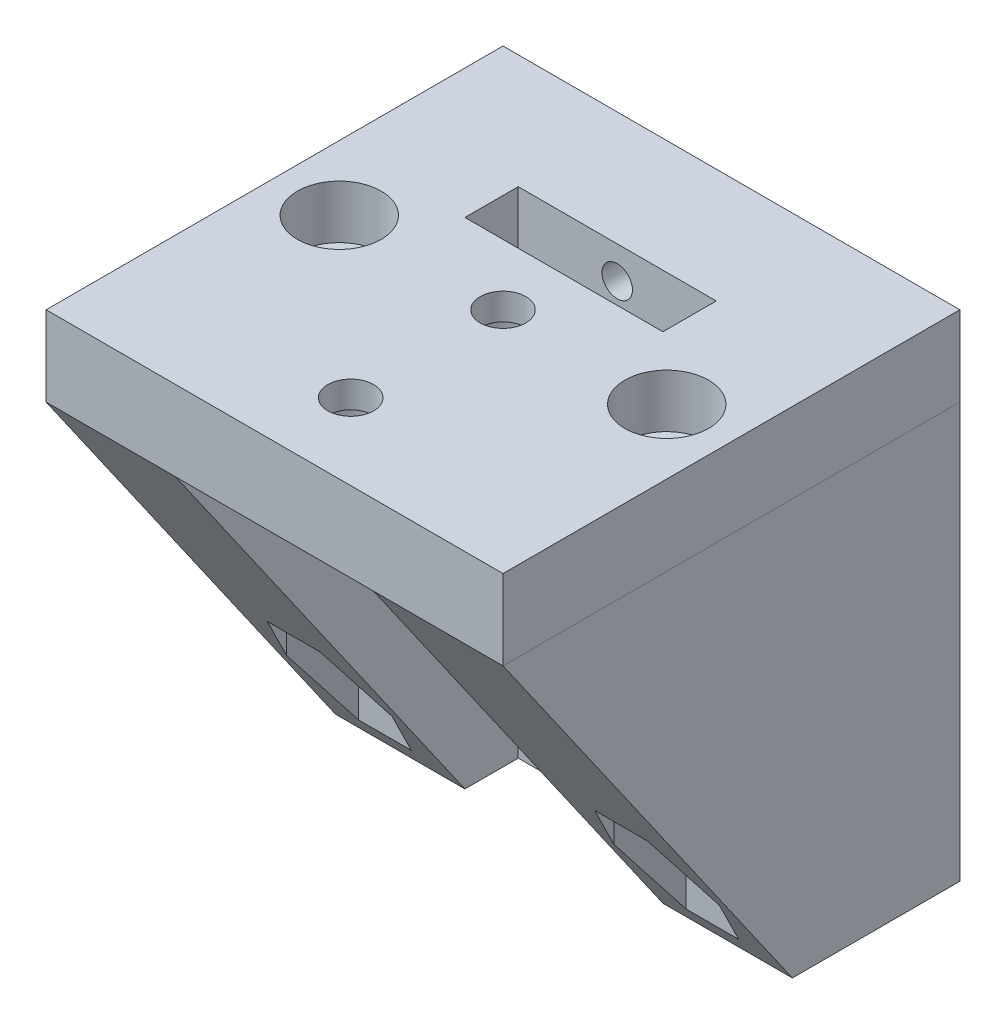
SolidWorks part; units mm, degrees
ref_plane "Front Plane" through (0, 0, 0) normal (0, 0, 1) x (1, 0, 0)
ref_plane "Top Plane" through (0, 0, 0) normal (0, 1, 0) x (1, 0, 0)
ref_plane "Right Plane" through (0, 0, 0) normal (1, 0, 0) x (0, 0, -1)
sketch "Sketch1" plane through (0, 0, 0) normal (0, 0, 1) x (1, 0, 0)
  line L0 (0, 0) -> (0, 50000) construction
  line L1 (0, 0) -> (50000, 0) construction
  line L2 (3.5, 6.35) -> (3.5, 5.2983)
  line L3 (-3.5, 6.35) -> (-3.5, 5.2983)
  line L4 (-15, 5.65) -> (49985, 5.65) construction
  line L5 (-15, -10.6) -> (15, -10.6)
  line L6 (-15, -10.6) -> (-15, 21.9)
  line L7 (-15, 21.9) -> (15, 21.9)
  line L8 (15, -10.6) -> (15, 21.9)
  line L9 (-6.5, -6.35) -> (6.5, -6.35)
  line L10 (-6.5, -6.35) -> (-6.5, 16.65)
  line L11 (-6.5, 16.65) -> (6.5, 16.65)
  line L12 (6.5, -6.35) -> (6.5, 16.65)
  arc A0 (-3.5, 5.2983) -> (3.5, 5.2983) centre (0, 0) ccw
  arc A1 (3.5, 6.35) -> (-3.5, 6.35) centre (0, 6.35) ccw
  arc A2 (-3.5, 5.2983) -> (3.5, 5.2983) centre (0, 0) ccw construction
  circle A3 centre (0, 0) radius 6.35 construction
  circle A4 centre (0, -8.475) radius 1
  circle A5 centre (0, 19.775) radius 1
  point P8 (0, -10.6)
  point P17 (0, -10.6)
  point P22 (0, 16.65)
  point P23 (0, -8.475)
  point P26 (-15, 5.65)
  dimension "D1" = 12.7
  dimension "D2" = 7
  dimension "D6" = 13
  dimension "D9" = 2
  dimension "D3" = 10.6
  dimension "D4" = 30
  dimension "D5" = 32.5
  dimension "D7" = 23
  dimension "D8" = 2.125
  dimension "D10" = 21.9
extrude "Boss-Extrude3" add sketch "Sketch1" along normal blind 1.5 contours L5 L8 L7 L6 L12 L9 L10 L11 A4 A5 region at (-14.5577, 5.65, 0)
sketch "Sketch6" plane through (0, 0, 0) normal (0, 0, -1) x (-1, 0, 0)
  line L1 (-15, -10.6) -> (15, -10.6)
  line L2 (-15, -10.6) -> (-15, 21.9)
  line L3 (-15, 21.9) -> (15, 21.9)
  line L4 (15, -10.6) -> (15, 21.9)
extrude "Boss-Extrude4" add sketch "Sketch6" along normal blind 6
extrude "Cut-Extrude1" cut sketch "Sketch1<3>" against normal up to surface (6 mm away) contours L2 A1 L3 A0 region at (0, 1.1131, 0) up to face at (0, 5.65, -6)
sketch "Sketch1<3>" plane through (0, 0, 0) normal (0, 0, 1) x (1, 0, 0) same geometry as "Sketch1"
sketch "Sketch7" plane through (0, 0, 1.5) normal (0, 0, 1) x (1, 0, 0)
  line L0 (-15, -10.6) -> (15, -10.6) construction
  line L2 (-15, 21.9) -> (-6.5, 21.9)
  line L3 (-15, 21.9) -> (-15, -10.6)
  line L4 (-15, -10.6) -> (-6.5, -10.6)
  line L5 (-6.5, 21.9) -> (-6.5, -10.6)
  line L6 (-15, 21.9) -> (15, 21.9) construction
  line L7 (15, -10.6) -> (6.5, -10.6)
  line L8 (15, -10.6) -> (15, 21.9)
  line L9 (15, 21.9) -> (6.5, 21.9)
  line L10 (6.5, -10.6) -> (6.5, 21.9)
  line L11 (6.5, -6.35) -> (6.5, 16.65) construction
  line L12 (-6.5, -6.35) -> (-6.5, 16.65) construction
extrude "Boss-Extrude5" add sketch "Sketch7" along normal blind 3.5
sketch "Sketch8" plane through (0, 0, 5) normal (0, 0, 1) x (1, 0, 0)
  line L0 (15, -10.6) -> (15, 21.9) construction
  line L1 (-15, 21.9) -> (15, 21.9)
  line L2 (-15, 21.9) -> (-15, 16.65)
  line L3 (-15, 16.65) -> (15, 16.65)
  line L4 (15, 21.9) -> (15, 16.65)
  line L5 (-6.5, 16.65) -> (6.5, 16.65) construction
extrude "Boss-Extrude6" add sketch "Sketch8" along normal blind 19
ref_plane "Plane1" through (15, 0, 0) normal (1, 0, 0) x (0, 0, -1)
sketch "Sketch9" plane through (15, 0, 0) normal (1, 0, 0) x (0, 0, -1)
  line L0 (-24, 16.65) -> (-5, 16.65)
  line L1 (-24, 16.65) -> (-5, 16.65) construction
  line L2 (-5, 16.65) -> (-5, -10.6)
  line L3 (-5, -10.6) -> (-24, 16.65)
extrude "Boss-Extrude7" add sketch "Sketch9" against normal up to surface (8.5 mm away) up to face at (6.5, 6.65, 2.3333)
ref_plane "Plane2" through (-15, 0, 0) normal (-1, 0, 0) x (0, 0, 1)
sketch "Sketch10" plane through (-15, 0, 0) normal (-1, 0, 0) x (0, 0, 1)
  line L0 (24, 16.65) -> (5, -10.6)
  line L1 (5, -10.6) -> (5, 16.65)
  line L2 (5, 16.65) -> (24, 16.65)
extrude "Boss-Extrude8" add sketch "Sketch10" against normal up to surface (8.5 mm away) up to face at (-6.5, 6.65, 2.3333)
sketch "Sketch12" plane through (0, 0, -6) normal (0, 0, -1) x (-1, 0, 0)
  line L0 (0, 0) -> (0, 50000) construction
  line L2 (2.3094, -8.6) -> (1.1547, -6.6)
  line L3 (1.1547, -6.6) -> (-1.1547, -6.6)
  line L4 (-1.1547, -6.6) -> (-2.3094, -8.6)
  line L5 (-2.3094, -8.6) -> (-1.1547, -10.6)
  line L6 (-1.1547, -10.6) -> (1.1547, -10.6)
  line L7 (1.1547, -10.6) -> (2.3094, -8.6)
  line L16 (-15, -10.6) -> (15, -10.6) construction
  circle A0 centre (0, -8.6) radius 2 construction
  dimension "D2" = 4
extrude "Cut-Extrude2" cut sketch "Sketch12" against normal blind 1.5
sketch "Sketch14" plane through (0, 0, 0) normal (0, 0, 1) x (1, 0, 0)
  line L0 (-1, -8.475) -> (49999, -8.475) construction
  line L1 (0, -7.475) -> (0, -50007.475) construction
  circle A4 centre (0, -8.475) radius 1
  dimension "D1" = 2
extrude "Cut-Extrude3" cut sketch "Sketch14" against normal up to surface (4.5 mm away) up to face at (0, -8.6, -4.5)
chamfer "Chamfer2" distance 1.1 angle 45 1 edges at (0, -6.35, 1.5)
sketch "Sketch15" plane through (0, 16.65, 0) normal (0, -1, 0) x (1, 0, 0)
  line L0 (-6.5, 24) -> (6.5, 24) construction
  line L1 (0, 24) -> (0, -49976) construction
  line L8 (15, -6) -> (1.1547, -6) construction
  circle A0 centre (0, 19) radius 2.75
  circle A1 centre (0, 9) radius 2.75
  point P2 (0, 24)
  dimension "D1" = 5.5
  dimension "D5" = 12.25
  dimension "D2" = 5
  dimension "D4" = 10
  dimension "D3" = 2
extrude "Cut-Extrude4" cut sketch "Sketch15" against normal blind 3.5
sketch "Sketch16" plane through (0, 20.15, 0) normal (0, -1, 0) x (1, 0, 0)
  circle A0 centre (0, 19) radius 1.5
  circle A1 centre (0, 9) radius 1.5
  dimension "D1" = 3
extrude "Cut-Extrude5" cut sketch "Sketch16" against normal up to surface (1.75 mm away) up to face at (0, 21.9, 9)
ref_plane "Plane3" through (0, 6.65, 0) normal (0, -1, 0) x (-1, 0, 0)
sketch "Sketch19" plane through (0, 6.65, 0) normal (0, -1, 0) x (-1, 0, 0)
  line L0 (0, -9) -> (50000, -9) construction
  line L1 (0, -9) -> (0, -50009) construction
  line L2 (-10.75, -24) -> (-10.75, 49976) construction
  line L3 (-6.5, -24) -> (-15, -24) construction
  line L4 (9.0179, -12) -> (7.2859, -9)
  line L5 (-7.2859, -9) -> (-9.0179, -6)
  line L6 (-9.0179, -6) -> (-12.4821, -6)
  line L7 (-12.4821, -6) -> (-14.2141, -9)
  line L8 (-14.2141, -9) -> (-12.4821, -12)
  line L9 (-12.4821, -12) -> (-9.0179, -12)
  line L10 (-9.0179, -12) -> (-7.2859, -9)
  line L11 (12.4821, -12) -> (9.0179, -12)
  line L12 (14.2141, -9) -> (12.4821, -12)
  line L13 (12.4821, -6) -> (14.2141, -9)
  line L14 (9.0179, -6) -> (12.4821, -6)
  line L15 (7.2859, -9) -> (9.0179, -6)
  circle A2 centre (-10.75, -9) radius 3 construction
  point P9 (-10.75, -24)
  point P10 (-10.75, -9)
  dimension "D1" = 6
extrude "Cut-Extrude6" cut sketch "Sketch19" along normal up to surface (7.2105 mm away) up to face at (-10.75, 3.025, 14.5)
sketch "Sketch20" plane through (0, 6.65, 0) normal (0, -1, 0) x (1, 0, 0)
  line L0 (0, 0) -> (0, 50000) construction
  line L1 (-10.75, 11.875) -> (-10.75, -49988.125) construction
  line L2 (-9.0179, 12) -> (-12.4821, 12) construction
  line L3 (-14.0698, 9) -> (49985.9302, 9) construction
  circle A0 centre (-10.75, 9) radius 1.5
  circle A1 centre (10.75, 9) radius 1.5
  point P7 (-10.75, 12)
  point P11 (-10.75, 9)
  dimension "D1" = 3
extrude "Cut-Extrude7" cut sketch "Sketch20" against normal up to surface (15.25 mm away) up to face at (0, 21.9, 20.5)
sketch "Sketch21" plane through (0, 21.9, 0) normal (0, 1, 0) x (1, 0, 0)
  line L0 (0, 0) -> (0, 50000) construction
  circle A0 centre (-10.75, -9) radius 2.75
  circle A1 centre (10.75, -9) radius 2.75
  dimension "D1" = 5.5
extrude "Cut-Extrude8" cut sketch "Sketch21" against normal blind 3.5 from offset 0
ref_plane "Plane5" through (0, 16.65, 0) normal (0, -1, 0) x (-1, 0, 0)
split "Split1" trim tools "Plane5" bodies to split 124 resulting bodies 125 126
